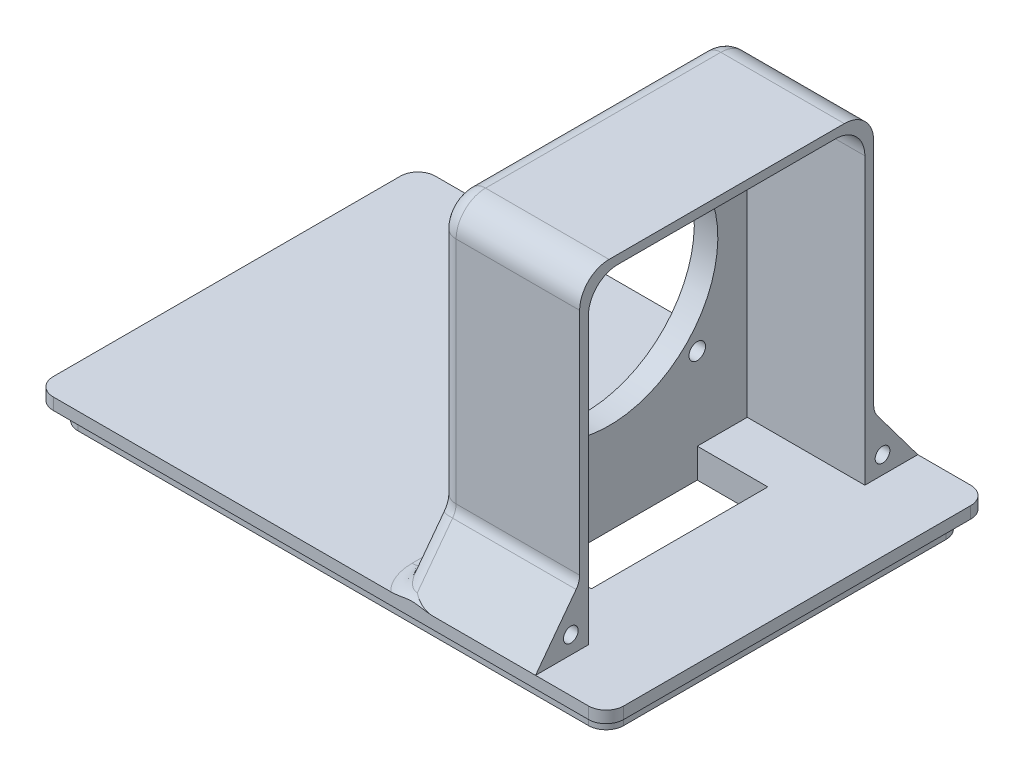
SolidWorks part; units mm, degrees
ref_plane "Front Plane" through (0, 0, 0) normal (0, 0, 1) x (1, 0, 0)
ref_plane "Top Plane" through (0, 0, 0) normal (0, 1, 0) x (1, 0, 0)
ref_plane "Right Plane" through (0, 0, 0) normal (1, 0, 0) x (0, 0, -1)
sketch "Sketch1" plane through (0, 0, 0) normal (0, 1, 0) x (1, 0, 0)
  line L1 (-48.5, 32.5) -> (48.5, 32.5)
  line L2 (-48.5, 32.5) -> (-48.5, -32.5)
  line L3 (-48.5, -32.5) -> (48.5, -32.5)
  line L4 (48.5, 32.5) -> (48.5, -32.5)
  line L5 (-48.5, 32.5) -> (48.5, -32.5) construction
  line L6 (-48.5, -32.5) -> (48.5, 32.5) construction
  point P0 (0, 0)
  dimension "D1" = 97
  dimension "D2" = 65
extrude "Boss-Extrude1" add sketch "Sketch1" along normal blind 2
fillet "Fillet1" radius 3 4 edges at (48.5, 1, -32.5) (48.5, 1, 32.5) (-48.5, 1, 32.5) (-48.5, 1, -32.5)
sketch "Sketch2" plane through (0, 0, 0) normal (0, -1, 0) x (1, 0, 0)
  line L4 (-48.5, -29.5) -> (-48.5, 29.5) construction
  line L5 (-46.4, -30.4) -> (46.4, -30.4)
  line L6 (-46.4, -30.4) -> (-46.4, 30.4)
  line L7 (-46.4, 30.4) -> (46.4, 30.4)
  line L8 (46.4, -30.4) -> (46.4, 30.4)
  line L9 (-46.4, -30.4) -> (46.4, 30.4) construction
  line L10 (-46.4, 30.4) -> (46.4, -30.4) construction
  line L11 (-45.5, 32.5) -> (45.5, 32.5) construction
  point P0 (0, 0)
  dimension "D1" = 2.1
  dimension "D2" = 2.1
extrude "Boss-Extrude2" add sketch "Sketch2" along normal blind 3
fillet "Fillet2" radius 3 4 edges at (46.4, -1.5, 30.4) (46.4, -1.5, -30.4) (-46.4, -1.5, -30.4) (-46.4, -1.5, 30.4)
ref_plane "Plane1" through (16.5, 0, 0) normal (1, 0, 0) x (0, 0, -1)
sketch "Sketch3" plane through (16.5, 0, 0) normal (1, 0, 0) x (0, 0, -1)
  line L0 (0, 0) -> (0, 43.8719) construction
  line L1 (-29.5, 2) -> (29.5, 2) construction
  line L2 (-32.5, 2) -> (-25, 12)
  line L4 (-25, 12) -> (-25, 57)
  line L5 (-25, 57) -> (25, 57)
  line L6 (25, 12) -> (25, 57)
  line L9 (32.5, 2) -> (25, 12)
  line L10 (-32.5, 2) -> (32.5, 2)
  circle A0 centre (0, 31) radius 18 construction
  dimension "D1" = 36
  dimension "D2" = 29
  dimension "D3" = 50
  dimension "D4" = 55
  dimension "D5" = 45
extrude "Boss-Extrude3" add sketch "Sketch3" against normal blind 4
sketch "Sketch4" plane through (16.5, 0, 0) normal (1, 0, 0) x (0, 0, -1)
  line L0 (0, 57) -> (0, 0) construction
  line L1 (25, 57) -> (-25, 57) construction
  line L2 (-29.5, 2) -> (29.5, 2) construction
  circle A0 centre (0, 31) radius 18.5
  dimension "D1" = 37
  dimension "D2" = 29
extrude "Cut-Extrude1" cut sketch "Sketch4" against normal up to next
sketch "Sketch5" plane through (16.5, 0, 0) normal (1, 0, 0) x (0, 0, -1)
  line L0 (0, 0) -> (0, 60.1416) construction
  line L8 (-5.5, 53.5) -> (5.5, 53.5)
  line L9 (-5.5, 53.5) -> (-5.5, 45.5)
  line L10 (-5.5, 45.5) -> (5.5, 45.5)
  line L11 (5.5, 53.5) -> (5.5, 45.5)
  line L12 (-5.5, 53.5) -> (5.5, 45.5) construction
  line L13 (-5.5, 45.5) -> (5.5, 53.5) construction
  circle A1 centre (0, 31) radius 18.5 construction
  point P3 (0, 49.5)
  dimension "D3" = 11
extrude "Cut-Extrude2" cut sketch "Sketch5" against normal up to next
sketch "Sketch6" plane through (16.5, 0, 0) normal (1, 0, 0) x (0, 0, -1)
  line L0 (-25, 57) -> (-25, 12) construction
  line L1 (25, 57) -> (-25, 57) construction
  line L2 (25, 12) -> (25, 57) construction
  line L3 (32.5, 2) -> (25, 12) construction
  line L4 (-32.5, 2) -> (32.5, 2) construction
  line L5 (-25, 12) -> (-32.5, 2) construction
  line L6 (-25, 57) -> (-25, 12)
  line L7 (25, 57) -> (-25, 57)
  line L8 (25, 12) -> (25, 57)
  line L9 (32.5, 2) -> (25, 12)
  line L11 (-25, 12) -> (-32.5, 2)
  line L13 (23.5, 11.5) -> (23.5, 55.5)
  line L14 (23.5, 55.5) -> (-23.5, 55.5)
  line L15 (-23.5, 55.5) -> (-23.5, 11.5)
  line L16 (23.5, 11.5) -> (23.5, 2)
  line L20 (31.3, 1.1) -> (23.5, 11.5) construction
  line L21 (-23.5, 11.5) -> (-31.3, 1.1) construction
  line L22 (-23.5, 11.5) -> (-23.5, 2)
  line L23 (-23.5, 2) -> (-32.5, 2)
  line L24 (23.5, 2) -> (32.5, 2)
  line M11 (25, 12) -> (25, 57)
  line M12 (25, 57) -> (-25, 57)
  line M13 (-25, 57) -> (-25, 12)
  line M14 (-25, 12) -> (-32.5, 2)
  line M15 (-32.5, 2) -> (32.5, 2)
  line M16 (32.5, 2) -> (25, 12)
  dimension "D1" = 1.5
extrude "Boss-Extrude4" add sketch "Sketch6" along normal blind 20 contours L15 L14 L13 M15 M16 M11 M12 M13 M14 region at (16.5, 56.1485, 0)
sketch "Sketch8" plane through (16.5, 0, 0) normal (1, 0, 0) x (0, 0, -1)
  line L0 (0, 55.5) -> (0, 0) construction
  line L1 (23.5, 55.5) -> (-23.5, 55.5) construction
  line L2 (-18.5, 31) -> (18.5, 31) construction
  arc A0 (-5.5, 48.6635) -> (5.5, 48.6635) centre (0, 31) ccw construction
  circle A1 centre (-15, 46) radius 1.4
  circle A2 centre (15, 46) radius 1.4
  circle A3 centre (15, 16) radius 1.4
  circle A4 centre (-15, 16) radius 1.4
  dimension "D1" = 2.8
  dimension "D2" = 30
  dimension "D3" = 30
extrude "Cut-Extrude3" cut sketch "Sketch8" against normal up to next
sketch "Sketch9" plane through (0, 2, 0) normal (0, 1, 0) x (1, 0, 0)
  line L0 (12.5, 0) -> (48.5, 0) construction
  line L1 (12.5, -32.5) -> (12.5, 32.5) construction
  line L2 (48.5, -29.5) -> (48.5, 29.5) construction
  line L3 (16.5, 15) -> (28.5, 15)
  line L4 (16.5, -29.7968) -> (16.5, 29.7968) construction
  line L5 (28.5, 15) -> (28.5, -15)
  line L6 (16.5, 15) -> (16.5, -15)
  line L7 (16.5, -15) -> (28.5, -15)
  point P13 (28.5, 0)
  point P14 (16.5, 0)
  dimension "D1" = 30
  dimension "D2" = 12
extrude "Cut-Extrude4" cut sketch "Sketch9" against normal through all
fillet "Fillet3" radius 3 7 edges at (24.5, 12, 25) (24.5, 12, -25) (12.5, 34.5, -25) (12.5, 7, -28.75) (12.5, 7, 28.75) (12.5, 34.5, 25) (12.5, 57, 0)
fillet "Fillet4" radius 3 3 edges at (13.3787, 2, 31.4017) (13.3787, 2, -31.4017) (12.5, 2, 0)
fillet "Fillet6" radius 5 2 edges at (26.5, 55.5, -23.5) (26.5, 55.5, 23.5)
fillet "Fillet7" radius 5 4 edges at (13.3787, 56.1213, 24.1213) (13.3787, 56.1213, -24.1213) (26, 57, -25) (26, 57, 25)
sketch "Sketch10" plane through (36.5, 0, 0) normal (1, 0, 0) x (0, 0, -1)
  line L0 (0, 55.5) -> (0, 0) construction
  line L1 (18.5, 55.5) -> (-18.5, 55.5) construction
  line L2 (27.4, 0) -> (-27.4, 0) construction
  line L3 (-29.5, 2) -> (29.5, 2) construction
  circle A0 centre (-26.5, 5) radius 1.25
  circle A1 centre (26.5, 5) radius 1.25
  dimension "D1" = 2.5
  dimension "D2" = 3
  dimension "D3" = 53
extrude "Cut-Extrude5" cut sketch "Sketch10" against normal blind 15
